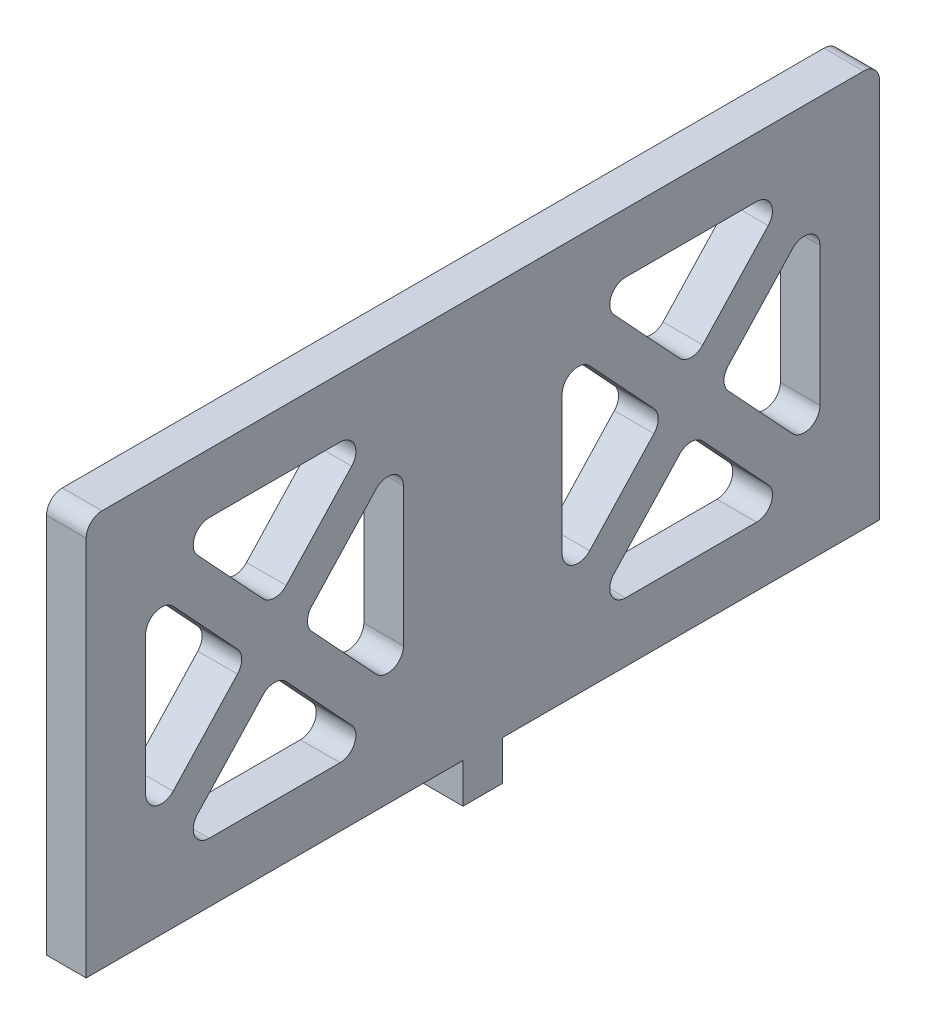
SolidWorks part; units mm, degrees
ref_plane "Front Plane" through (0, 0, 0) normal (0, 0, 1) x (1, 0, 0)
ref_plane "Top Plane" through (0, 0, 0) normal (0, 1, 0) x (1, 0, 0)
ref_plane "Right Plane" through (0, 0, 0) normal (1, 0, 0) x (0, 0, -1)
sketch "Sketch4" plane through (0, 0, 0) normal (1, 0, 0) x (0, 0, -1)
  line L0 (0, 6.35) -> (-60.325, 6.35)
  line L1 (0, 0) -> (6.35, 0)
  line L2 (0, 0) -> (0, 6.35)
  line L3 (0, 6.35) -> (6.35, 6.35) construction
  line L4 (6.35, 0) -> (6.35, 6.35)
  line L5 (6.35, 6.35) -> (66.675, 6.35)
  line L6 (66.675, 6.35) -> (66.675, 69.85)
  line L7 (66.675, 69.85) -> (-60.325, 69.85)
  line L8 (-60.325, 69.85) -> (-60.325, 6.35)
  line L9 (3.175, 6.35) -> (3.175, 26.8663) construction
  dimension "D1" = 6.35
  dimension "D2" = 6.35
  dimension "D3" = 60.325
  dimension "D4" = 63.5
extrude "Boss-Extrude1" add sketch "Sketch4" along normal blind 6.35
sketch "Sketch5" plane through (6.35, 0, 0) normal (1, 0, 0) x (0, 0, -1)
  line L0 (66.675, 6.35) -> (66.675, 69.85) construction
  line L1 (-50.8, 60.325) -> (57.15, 60.325)
  line L2 (-50.8, 60.325) -> (-50.8, 15.875)
  line L3 (-50.8, 15.875) -> (57.15, 15.875)
  line L4 (57.15, 60.325) -> (57.15, 15.875)
  line L5 (66.675, 69.85) -> (-60.325, 69.85) construction
  line L6 (-60.325, 69.85) -> (-60.325, 6.35) construction
  line L7 (-60.325, 6.35) -> (0, 6.35) construction
  line L8 (3.175, 60.325) -> (3.175, 15.875) construction
  line L9 (-9.525, 60.325) -> (15.875, 60.325)
  line L10 (-9.525, 60.325) -> (-9.525, 15.875)
  line L11 (-9.525, 15.875) -> (15.875, 15.875)
  line L12 (15.875, 60.325) -> (15.875, 15.875)
  line L13 (15.875, 15.875) -> (57.15, 60.325) construction
  line L14 (13.5484, 18.0354) -> (54.8234, 62.4854)
  line L15 (18.2016, 13.7146) -> (59.4766, 58.1646)
  line L16 (57.15, 15.875) -> (15.875, 60.325) construction
  line L17 (54.8234, 13.7146) -> (13.5484, 58.1646)
  line L18 (59.4766, 18.0354) -> (18.2016, 62.4854)
  line L19 (-9.525, 15.875) -> (-50.8, 60.325) construction
  line L20 (-7.1984, 18.0354) -> (-48.4734, 62.4854)
  line L21 (-11.8516, 13.7146) -> (-53.1266, 58.1646)
  line L22 (-50.8, 15.875) -> (-9.525, 60.325) construction
  line L23 (-48.4734, 13.7146) -> (-7.1984, 58.1646)
  line L24 (-53.1266, 18.0354) -> (-11.8516, 62.4854)
  arc A0 (13.5484, 18.0354) -> (18.2016, 13.7146) centre (15.875, 15.875) ccw
  arc A1 (59.4766, 58.1646) -> (54.8234, 62.4854) centre (57.15, 60.325) ccw
  arc A2 (54.8234, 13.7146) -> (59.4766, 18.0354) centre (57.15, 15.875) ccw
  arc A3 (18.2016, 62.4854) -> (13.5484, 58.1646) centre (15.875, 60.325) ccw
  arc A4 (-7.1984, 18.0354) -> (-11.8516, 13.7146) centre (-9.525, 15.875) cw
  arc A5 (-53.1266, 58.1646) -> (-48.4734, 62.4854) centre (-50.8, 60.325) cw
  arc A6 (-48.4734, 13.7146) -> (-53.1266, 18.0354) centre (-50.8, 15.875) cw
  arc A7 (-11.8516, 62.4854) -> (-7.1984, 58.1646) centre (-9.525, 60.325) cw
  point P18 (36.5125, 38.1)
  point P23 (36.5125, 38.1)
  point P28 (-30.1625, 38.1)
  point P33 (-30.1625, 38.1)
  dimension "D6" = 3.175
  dimension "D1" = 9.525
  dimension "D2" = 9.525
  dimension "D3" = 9.525
  dimension "D4" = 9.525
  dimension "D5" = 25.4
extrude "Cut-Extrude1" cut sketch "Sketch5" against normal through all contours L2 L24 L21 | L20 L24 L1 | L23 L20 L10 | L23 L3 L21 | L14 L17 L12 | L18 L14 L1 | L18 L4 L15 | L3 L17 L15 region at (6.35, 54.472, 30.1625) region at (6.35, 38.1, 45.3651) region at (6.35, 38.1, 14.9599) region at (6.35, 21.728, 30.1625) region at (6.35, 54.472, -36.5125) region at (6.35, 38.1, -21.3099) region at (6.35, 38.1, -51.7151) region at (6.35, 21.728, -36.5125)
fillet "Fillet1" radius 2.54 24 edges at (3.175, 33.434, 30.1625) (3.175, 15.875, 13.8577) (3.175, 15.875, 46.4673) (3.175, 55.659, 9.525) (3.175, 20.541, 9.525) (3.175, 38.1, 25.8298) (3.175, 33.434, -36.5125) (3.175, 15.875, -52.8173) (3.175, 15.875, -20.2077) (3.175, 38.1, -40.8452) (3.175, 55.659, -57.15) (3.175, 20.541, -57.15) (3.175, 38.1, 34.4952) (3.175, 20.541, 50.8) (3.175, 55.659, 50.8) (3.175, 60.325, -20.2077) (3.175, 60.325, -52.8173) (3.175, 42.766, -36.5125) (3.175, 60.325, 13.8577) (3.175, 42.766, 30.1625) (3.175, 55.659, -15.875) (3.175, 38.1, -32.1798) (3.175, 20.541, -15.875) (3.175, 60.325, 46.4673)
fillet "Fillet2" radius 2.54 2 edges at (3.175, 69.85, -66.675) (3.175, 69.85, 60.325)
